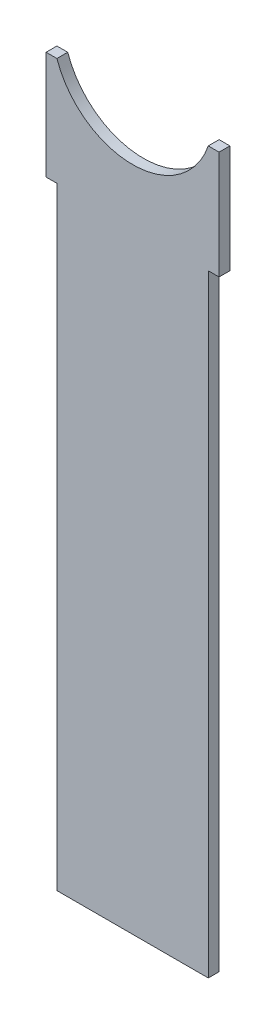
SolidWorks part; units mm, degrees
material "AISI 4130 Steel, annealed at 865C"
ref_plane "X-Y Datum" through (0, 0, 0) normal (0, 0, 1) x (1, 0, 0)
ref_plane "X-Z Datum" through (0, 0, 0) normal (0, 1, 0) x (1, 0, 0)
ref_plane "Y-Z Datum" through (0, 0, 0) normal (1, 0, 0) x (0, 0, -1)
sketch "Sketch2" plane through (0, 0, 0) normal (0, 0, 1) x (1, 0, 0)
  line L0 (-12.7, -7.9375) -> (12.7, -7.9375) construction
  line L2 (-11.1125, 0) -> (-11.1125, -105.8046)
  line L3 (-11.1125, -105.8046) -> (11.1125, -105.8046)
  line L4 (11.1125, 0) -> (11.1125, -105.8046)
  line L5 (-11.1125, -15.875) -> (-12.7, -15.875)
  line L6 (-11.1125, -15.875) -> (-11.1125, 0)
  line L7 (-11.1125, 0) -> (-12.7, 0)
  line L8 (-12.7, -15.875) -> (-12.7, 0)
  line L9 (11.1125, -15.875) -> (12.7, -15.875)
  line L10 (11.1125, -15.875) -> (11.1125, 0)
  line L11 (11.1125, 0) -> (12.7, 0)
  line L12 (12.7, -15.875) -> (12.7, 0)
  line L13 (-11.1125, -105.8046) -> (-12.7, -105.8046) construction
  arc A1 (-11.1125, 0) -> (11.1125, 0) centre (0, 3.81) ccw
  point P0 (0, -105.8046)
  dimension "D1" = 1.5875
  dimension "D2" = 25.4
  dimension "D4" = 15.875
extrude "Boss-Extrude1" add sketch "Sketch2" along normal blind 1.5875 contours L0 L6 L2 L3 L4 L10 | A1 L0 L4 | L4 L0 L12 L11 | L0 L10 L9 L12 | L0 L8 L5 L6 | L8 L0 L2 L7 | L2 L0 A1 region at (-11.9062, -3.9687, 0) region at (-11.9062, -11.9062, 0) region at (-8.5529, -5.8085, 0) region at (0, -56.871, 0) region at (8.5529, -5.8085, 0) region at (11.9062, -3.9687, 0) region at (11.9062, -11.9062, 0)
